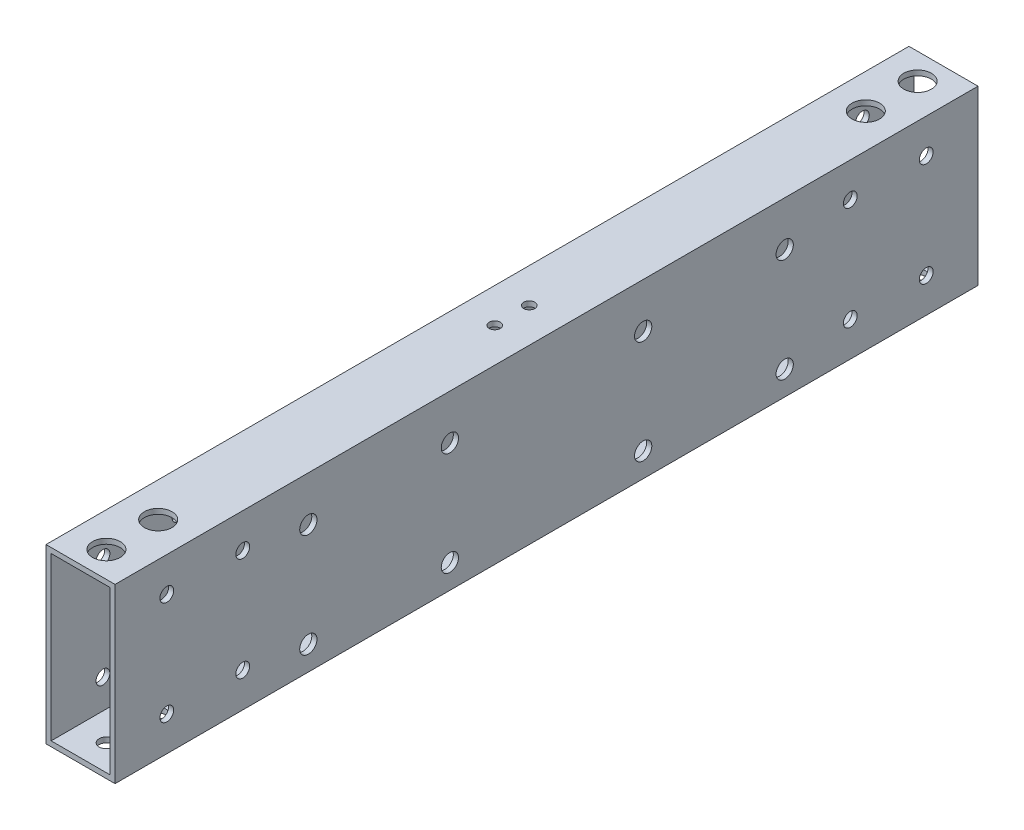
SolidWorks part; units mm, degrees
ref_plane "前视基准面" through (0, 0, 0) normal (0, 0, 1) x (1, 0, 0)
ref_plane "上视基准面" through (0, 0, 0) normal (0, 1, 0) x (1, 0, 0)
ref_plane "右视基准面" through (0, 0, 0) normal (1, 0, 0) x (0, 0, -1)
sketch "草图1" plane through (0, 0, 0) normal (0, 0, 1) x (1, 0, 0)
  line L0 (-8.5, 23.5) -> (8.5, 23.5)
  line L1 (-10, -25) -> (10, -25)
  line L2 (-10, -25) -> (-10, 25)
  line L3 (-10, 25) -> (10, 25)
  line L4 (10, -25) -> (10, 25)
  line L5 (-10, -25) -> (10, 25) construction
  line L6 (-10, 25) -> (10, -25) construction
  line L11 (8.5, -23.5) -> (8.5, 23.5)
  line L12 (-8.5, -23.5) -> (8.5, -23.5)
  line L13 (-8.5, -23.5) -> (-8.5, 23.5)
  point P9 (0, 0)
  dimension "D1" = 50
  dimension "D2" = 20
  dimension "D3" = 1.5
extrude "凸台-拉伸1" add sketch "草图1" against normal blind 250
sketch "草图2" plane through (-10, 0, 0) normal (-1, 0, 0) x (0, 0, 1)
  line L0 (-125, 20) -> (-125, -49980) construction
  line L1 (-250, 25) -> (0, 25) construction
  line L2 (-250, 25) -> (0, 25) construction
  line L11 (-56, -18) -> (-97, -18) construction
  line L13 (-56, -18) -> (-56, 12) construction
  line L14 (-56, 12) -> (-97, 12) construction
  line L15 (-97, -18) -> (-97, 12) construction
  line L16 (-56, -18) -> (-97, 12) construction
  line L17 (-56, 12) -> (-97, -18) construction
  line L18 (-71.3284, -3) -> (-50071.3284, -3) construction
  line L19 (-76.5, -3) -> (-76.5, 49997) construction
  line L20 (-194, 12) -> (-153, -18) construction
  line L21 (-194, -18) -> (-153, 12) construction
  line L22 (-153, -18) -> (-153, 12) construction
  line L23 (-194, 12) -> (-153, 12) construction
  line L24 (-194, -18) -> (-194, 12) construction
  line L25 (-194, -18) -> (-153, -18) construction
  line L26 (0, -25) -> (0, 25) construction
  circle A16 centre (-56, 12) radius 2.5
  circle A17 centre (-97, 12) radius 2.5
  circle A18 centre (-97, -18) radius 2.5
  circle A19 centre (-56, -18) radius 2.5
  circle A20 centre (-194, -18) radius 2.5
  circle A21 centre (-153, -18) radius 2.5
  circle A22 centre (-153, 12) radius 2.5
  circle A23 centre (-194, 12) radius 2.5
  point P4 (-125, 25)
  point P5 (-76.5, -3)
  point P28 (-173.5, -3)
  dimension "D4" = 5
  dimension "D5" = 76.5
  dimension "D2" = 41
  dimension "D1" = 30
  dimension "D3" = 28
extrude "切除-拉伸1" cut sketch "草图2" against normal through all
sketch "草图3" plane through (0, 25, 0) normal (0, 1, 0) x (1, 0, 0)
  line L0 (-10, 30) -> (49990, 30) construction
  line L2 (10, 0) -> (-10, 0) construction
  line L3 (0, 0) -> (0, 50000) construction
  line L4 (10, 125) -> (50010, 125) construction
  line L5 (10, 250) -> (10, 0) construction
  circle A0 centre (0, 22.5) radius 2.1
  circle A1 centre (0, 7.5) radius 2.1
  circle A2 centre (0, 242.5) radius 2.1
  circle A3 centre (0, 227.5) radius 2.1
  point P6 (0, 0)
  point P15 (10, 125)
  dimension "D2" = 4.2
  dimension "D3" = 4.2
  dimension "D1" = 30
  dimension "D4" = 15
  dimension "D5" = 7.5
extrude "切除-拉伸2" cut sketch "草图3" against normal through all
sketch "草图4" plane through (0, 25, 0) normal (0, 1, 0) x (1, 0, 0)
  line L0 (0, 250) -> (0, -49750) construction
  line L1 (10, 250) -> (-10, 250) construction
  line L2 (-10, 125) -> (49990, 125) construction
  line L3 (-10, 250) -> (-10, 0) construction
  circle A0 centre (0, 130) radius 1.6
  circle A1 centre (0, 120) radius 1.6
  point P4 (0, 250)
  point P9 (-10, 125)
  dimension "D1" = 3.2
  dimension "D2" = 10
extrude "切除-拉伸3" cut sketch "草图4" against normal blind 10
sketch "草图5" plane through (0, 25, 0) normal (0, 1, 0) x (1, 0, 0)
  line L0 (10, 125) -> (50010, 125) construction
  line L1 (10, 250) -> (10, 0) construction
  circle A0 centre (0, 22.5) radius 4
  circle A1 centre (0, 7.5) radius 4
  circle A2 centre (0, 242.5) radius 4
  circle A3 centre (0, 227.5) radius 4
  point P10 (10, 125)
  dimension "D1" = 8
  dimension "D2" = 8
extrude "切除-拉伸4" cut sketch "草图5" against normal blind 10
sketch "草图6" plane through (-10, 0, 0) normal (-1, 0, 0) x (0, 0, 1)
  line L0 (-125, 25) -> (-125, -75.8071) construction
  line L1 (-250, 25) -> (0, 25) construction
  circle A0 centre (-125, -4) radius 7.5
  dimension "D1" = 15
  dimension "D2" = 4
extrude "切除-拉伸5" cut sketch "草图6" against normal blind 10
sketch "草图7" plane through (-10, 0, 0) normal (-1, 0, 0) x (0, 0, 1)
  line L0 (-250, 0) -> (0, 0) construction
  line L1 (-250, 25) -> (-250, -25) construction
  line L2 (-125, 25) -> (-125, -25) construction
  line L3 (-250, 25) -> (0, 25) construction
  line L4 (-250, -25) -> (0, -25) construction
  line L5 (-250, 15) -> (0, 15) construction
  line L6 (0, 25) -> (0, -25) construction
  line L7 (-250, -15) -> (0, -15) construction
  circle A0 centre (-235, 15) radius 2
  circle A1 centre (-213, 15) radius 2
  circle A2 centre (-235, -15) radius 2
  circle A3 centre (-213, -15) radius 2
  circle A5 centre (-37, -15) radius 2
  circle A6 centre (-15, -15) radius 2
  circle A7 centre (-37, 15) radius 2
  circle A8 centre (-15, 15) radius 2
  dimension "D3" = 4
  dimension "D1" = 15
  dimension "D2" = 15
  dimension "D4" = 22
  dimension "D5" = 15
extrude "切除-拉伸6" cut sketch "草图7" against normal through all
sketch "草图8" plane through (10, 0, 0) normal (1, 0, 0) x (0, 0, -1)
  line L0 (125, 25) -> (125, -58.3352) construction
  line L1 (250, 25) -> (0, 25) construction
  line L2 (138.5, 25) -> (138.5, -3.973)
  line L3 (138.5, 25) -> (111.5, 25)
  line L4 (125, 25) -> (125, -3.973)
  line L5 (138.5, -3.973) -> (111.5, -3.973)
  line L6 (111.5, 25) -> (111.5, -3.973)
  line M24 (250, 25) -> (0, 25)
  dimension "D1" = 27
extrude "切除-拉伸7" [suppressed] cut sketch "草图8" against normal blind 37 contours L5 L2 L4 M24 | L3 L6 L5 L4
equation "\"3。2\"=3.21956"
